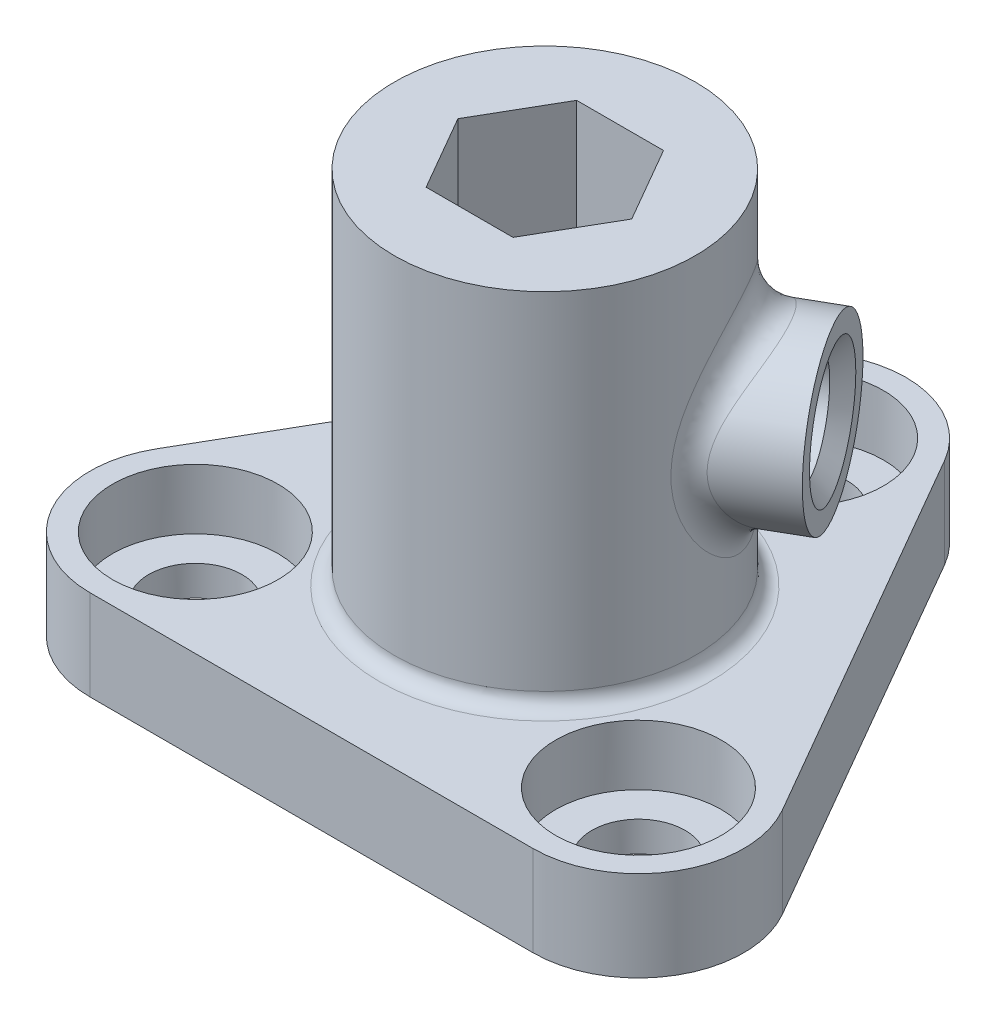
SolidWorks part; units mm, degrees
ref_plane "Front Plane" through (0, 0, 0) normal (0, 0, 1) x (1, 0, 0)
ref_plane "Top Plane" through (0, 0, 0) normal (0, 1, 0) x (1, 0, 0)
ref_plane "Right Plane" through (0, 0, 0) normal (1, 0, 0) x (0, 0, -1)
sketch "Sketch1" plane through (0, 0, 0) normal (1, 0, 0) x (0, 0, -1)
  line L1 (0, 0) -> (12, 0)
  line L2 (0, 0) -> (0, 5.3535)
  line L3 (5, 3) -> (12, 3)
  line L4 (12, 0) -> (12, 3)
  line L6 (0, 5.3535) -> (0, 15)
  line L7 (0, 15) -> (5, 15)
  line L8 (5, 3) -> (5, 15)
  dimension "D1" = 15
  dimension "6" = 5
  dimension "D3" = 3
  dimension "D4" = 7
revolve "Revolve1" add sketch "Sketch1" angle 360 about L6
sketch "Sketch4" plane through (0, 3, 0) normal (0, 1, 0) x (1, 0, 0)
  circle A0 centre (0, 8.5) radius 2.75
  circle A1 centre (7.3612, -4.25) radius 2.75
  circle A2 centre (-7.3612, -4.25) radius 2.75
  circle A6 centre (0, 0) radius 8.5 construction
  point P15 (0, 0)
  dimension "D2" = 17
  dimension "D3" = 5.5
  dimension "D1" = 3
extrude "Cut-Extrude4" cut sketch "Sketch4" against normal offset from surface (2 mm away) 1 up to face at (0, 0, -12)
sketch "Sketch5" plane through (0, 3, 0) normal (0, 1, 0) x (1, 0, 0)
  line L0 (-3.0311, 10.25) -> (-10.3923, -2.5)
  line L1 (-7.3612, -7.75) -> (7.3612, -7.75)
  line L2 (3.0311, 10.25) -> (10.3923, -2.5)
  arc A0 (3.0311, 10.25) -> (-3.0311, 10.25) centre (0, 8.5) ccw
  arc A1 (7.3612, -7.75) -> (10.3923, -2.5) centre (7.3612, -4.25) ccw
  arc A2 (-10.3923, -2.5) -> (-7.3612, -7.75) centre (-7.3612, -4.25) ccw
  circle A3 centre (0, 0) radius 12 construction
extrude "Cut-Extrude5" cut sketch "Sketch5" against normal through all flip side to cut
sketch "Sketch2" plane through (0, 15, 0) normal (0, 1, 0) x (1, 0, 0)
  line L0 (10.3923, -2.5) -> (3.0311, 10.25) construction
  line L1 (2.8868, 0) -> (1.4434, 2.5)
  line L2 (1.4434, 2.5) -> (-1.4434, 2.5)
  line L3 (-1.4434, 2.5) -> (-2.8868, 0)
  line L4 (-2.8868, 0) -> (-1.4434, -2.5)
  line L5 (-1.4434, -2.5) -> (1.4434, -2.5)
  line L6 (1.4434, -2.5) -> (2.8868, 0)
  circle A0 centre (0, 0) radius 2.5 construction
  dimension "D1" = 5
extrude "Cut-Extrude2" cut sketch "Sketch2" against normal offset from surface (8 mm away) 4 up to face at (0, 3, -5.75)
ref_plane "Plane1" through (6.0622, 0, -3.5) normal (-0.866, 0, 0.5) x (0.5, 0, 0.866)
sketch "Sketch3" plane through (6.0622, 0, -3.5) normal (0.866, 0, -0.5) x (-0.5, 0, -0.866)
  line L0 (0, 15) -> (0, 3) construction
  line L1 (1.4434, 15) -> (-1.4434, 15) construction
  line L3 (5, 3) -> (-5, 3) construction
  circle A0 centre (0, 9) radius 2.75
  point P10 (0, 9)
  dimension "D1" = 5.5
extrude "Boss-Extrude1" add sketch "Sketch3" against normal up to next
sketch "Sketch6" plane through (6.0622, 0, -3.5) normal (0.866, 0, -0.5) x (-0.5, 0, -0.866)
  circle A0 centre (0, 9) radius 1.6
  dimension "D1" = 3.2
extrude "Cut-Extrude6" cut sketch "Sketch6" against normal up to next
fillet "Fillet1" radius 0.5 1 edges at (0, 3, -5)
chamfer "Chamfer1" distance 0.5 angle 45 1 edges at (5.2622, 9, -4.8856)
fillet "Fillet2" radius 1 1 edges at (4.9921, 8.766, 0.2817)
sketch "Sketch7" plane through (0, 3, 0) normal (0, 1, 0) x (1, 0, 0)
  circle A0 centre (0, 8.5) radius 1.55
  circle A1 centre (7.3612, -4.25) radius 1.55
  circle A2 centre (-7.3612, -4.25) radius 1.55
  dimension "D1" = 3.1
extrude "Cut-Extrude7" cut sketch "Sketch7" against normal through all
